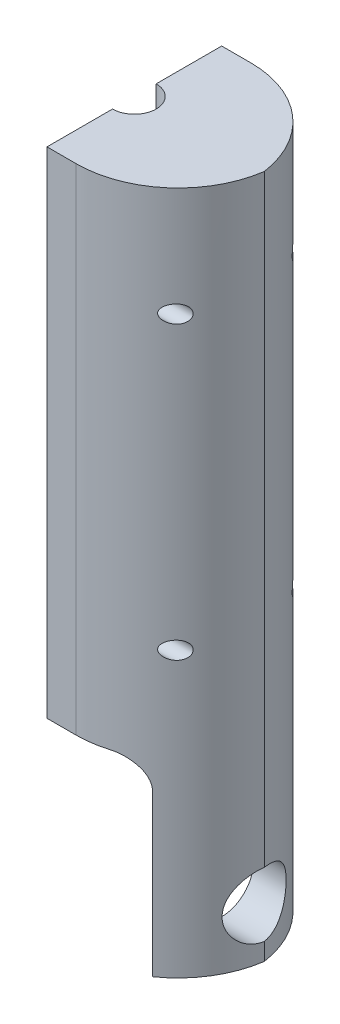
SolidWorks part; units mm, degrees
ref_plane "Plan de face" through (0, 0, 0) normal (0, 0, 1) x (1, 0, 0)
ref_plane "Plan de dessus" through (0, 0, 0) normal (0, 1, 0) x (1, 0, 0)
ref_plane "Plan de droite" through (0, 0, 0) normal (1, 0, 0) x (0, 0, -1)
sketch "Esquisse1" plane through (0, 0, 0) normal (0, 0, 1) x (1, 0, 0)
  line L0 (-139.3911, 131.107) -> (-139.3911, -98.893)
  line L1 (-139.3911, -98.893) -> (-124.3911, -98.893)
  line L2 (-124.3911, -98.893) -> (-124.3911, -33.893)
  line L3 (-124.3911, -33.893) -> (-64.3911, -33.893)
  line L4 (-64.3911, -33.893) -> (-64.3911, -98.893)
  line L5 (-64.3911, -98.893) -> (-49.3911, -98.893)
  line L6 (-49.3911, -98.893) -> (-49.3911, 131.107)
  line L7 (-49.3911, 131.107) -> (-139.3911, 131.107)
  dimension "D1" = 230
  dimension "D2" = 90
  dimension "D3" = 60
  dimension "D4" = 15
extrude "Boss.-Extru.1" add sketch "Esquisse1" along normal blind 60
fillet "Congé4" radius 35 1 edges at (-139.3911, 16.107, 60)
fillet "Congé5" radius 35 1 edges at (-139.3911, 16.107, 0)
fillet "Congé6" radius 35 2 edges at (-49.3911, 16.107, 0) (-49.3911, 16.107, 60)
fillet "Congé12" radius 10 2 edges at (-124.3911, -33.893, 29.5186) (-64.3911, -33.893, 30)
sketch "Esquisse3" plane through (-64.3911, 0, 0) normal (-1, 0, 0) x (0, 0, 1)
  line L0 (30, -98.893) -> (30, -64.9421) construction
  line L1 (53.7228, -98.893) -> (6.2772, -98.893) construction
  circle A1 centre (30, -81.9176) radius 11
  dimension "D1" = 22
extrude "Enlèv. mat.-Extru.4" cut sketch "Esquisse3" against normal blind 50
sketch "Esquisse5" plane through (0, 131.107, 0) normal (0, 1, 0) x (1, 0, 0)
  line L0 (-94.3911, -60) -> (-94.3911, 0)
  line L1 (-84.3911, -60) -> (-104.3911, -60) construction
  arc A0 (-94.3911, -60) -> (-94.3911, 0) centre (-123.4668, -30) cw
extrude "Enlèv. mat.-Extru.8" cut sketch "Esquisse5" against normal blind 251
sketch "Esquisse6" plane through (-94.3911, 0, 0) normal (-1, 0, 0) x (0, 0, 1)
  line L0 (30, 131.107) -> (30, -33.893) construction
  line L1 (60, 131.107) -> (0, 131.107) construction
  line L2 (60, -33.893) -> (0, -33.893) construction
  line L4 (60, -33.893) -> (60, 131.107) construction
  line L5 (60, 48.607) -> (0, 48.607) construction
  line L6 (0, -33.893) -> (0, 131.107) construction
  circle A0 centre (10, 98.607) radius 2
  circle A1 centre (50, 98.607) radius 2
  circle A2 centre (50, -1.393) radius 2
  circle A3 centre (10, -1.393) radius 2
  dimension "D1" = 40
  dimension "D2" = 50
extrude "Enlèv. mat.-Extru.9" cut sketch "Esquisse6" against normal blind 58
sketch "Esquisse9" plane through (0, 131.107, 0) normal (0, 1, 0) x (1, 0, 0)
  line L0 (-94.3911, -60) -> (-94.3911, 0) construction
  line L1 (-49.7501, -30) -> (-94.3911, -30) construction
  arc A0 (-94.3911, -22.5) -> (-94.3911, -37.5) centre (-94.3911, -30) cw
  point P8 (-86.8911, -30)
  dimension "D1" = 15
extrude "Enlèv. mat.-Extru.12" cut sketch "Esquisse9" against normal blind 179 and the other way through all flip side to cut
shell "Coque1" thickness 5 removed face at (-82.4875, 131.107, 30)
ref_plane "Plan2" through (-49.7501, 0, 0) normal (-1, 0, 0) x (0, 0, 1)
sketch "Esquisse11" plane through (-49.7501, 0, 0) normal (-1, 0, 0) x (0, 0, 1)
  circle A0 centre (50, -1.393) radius 2 construction
  circle A1 centre (50, 98.607) radius 2 construction
  circle A2 centre (50, -1.393) radius 2
  circle A3 centre (50, 98.607) radius 2
  circle A4 centre (10, 98.607) radius 2 construction
  circle A5 centre (10, -1.393) radius 2 construction
  circle A6 centre (10, 98.607) radius 2
  circle A7 centre (10, -1.393) radius 2
  circle A8 centre (50, 98.607) radius 3
  circle A9 centre (10, 98.607) radius 3
  circle A10 centre (50, -1.393) radius 3
  circle A11 centre (10, -1.393) radius 3
extrude "Enlèv. mat.-Extru.14" cut sketch "Esquisse11" along normal blind 20
sketch "Esquisse12" plane through (0, 131.107, 0) normal (0, 1, 0) x (1, 0, 0)
  line L0 (-84.3911, 0) -> (-94.3911, 0) construction
  line L1 (-94.3911, -22.5) -> (-94.3911, 0) construction
  line L2 (-94.3911, -60) -> (-94.3911, -37.5) construction
  line L3 (-84.3911, -60) -> (-94.3911, -60) construction
  line L4 (-84.3911, 0) -> (-94.3911, 0)
  line L5 (-94.3911, -22.5) -> (-94.3911, 0)
  line L6 (-94.3911, -60) -> (-94.3911, -37.5)
  line L7 (-84.3911, -60) -> (-94.3911, -60)
  arc A0 (-94.3911, -37.5) -> (-94.3911, -22.5) centre (-94.3911, -30) ccw construction
  arc A1 (-84.3911, -60) -> (-49.7501, -30) centre (-84.3911, -25) ccw construction
  arc A2 (-49.7501, -30) -> (-84.3911, 0) centre (-84.3911, -35) ccw construction
  arc A3 (-94.3911, -37.5) -> (-94.3911, -22.5) centre (-94.3911, -30) ccw
  arc A4 (-84.3911, -60) -> (-49.7501, -30) centre (-84.3911, -25) ccw
  arc A5 (-49.7501, -30) -> (-84.3911, 0) centre (-84.3911, -35) ccw
extrude "Boss.-Extru.2" add sketch "Esquisse12" along normal blind 5
